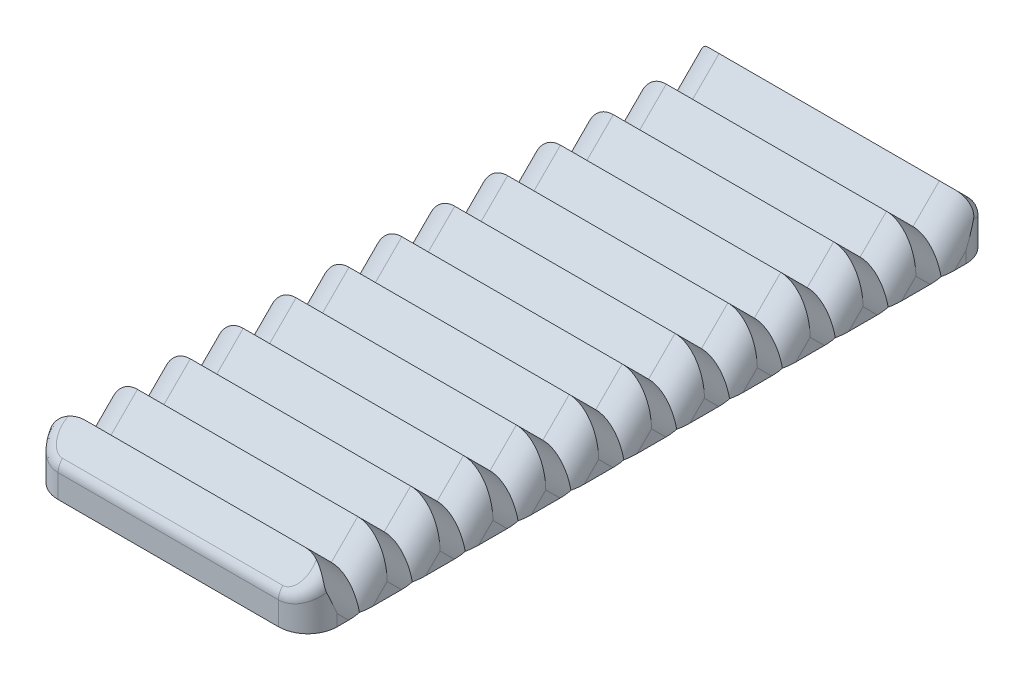
SolidWorks part; units mm, degrees
ref_plane "Front Plane" through (0, 0, 0) normal (0, 0, 1) x (1, 0, 0)
ref_plane "Top Plane" through (0, 0, 0) normal (0, 1, 0) x (1, 0, 0)
ref_plane "Right Plane" through (0, 0, 0) normal (1, 0, 0) x (0, 0, -1)
sketch "Sketch1" plane through (0, 0, 0) normal (1, 0, 0) x (0, 0, -1)
  line L0 (0, 0) -> (0.9, 0.9)
  line L1 (0.9, 0.9) -> (1.8, 0)
  line L2 (0, 0) -> (1.8, 0) construction
  line L3 (1.8, 0) -> (2.7, 0.9)
  line L4 (2.7, 0.9) -> (3.6, 0)
  line L5 (1.8, 0) -> (3.6, 0) construction
  line L6 (3.6, 0) -> (4.5, 0.9)
  line L7 (4.5, 0.9) -> (5.4, 0)
  line L8 (3.6, 0) -> (5.4, 0) construction
  line L9 (5.4, 0) -> (6.3, 0.9)
  line L10 (6.3, 0.9) -> (7.2, 0)
  line L11 (5.4, 0) -> (7.2, 0) construction
  line L12 (7.2, 0) -> (8.1, 0.9)
  line L13 (8.1, 0.9) -> (9, 0)
  line L14 (7.2, 0) -> (9, 0) construction
  line L15 (9, 0) -> (9.9, 0.9)
  line L16 (9.9, 0.9) -> (10.8, 0)
  line L17 (9, 0) -> (10.8, 0) construction
  line L18 (10.8, 0) -> (11.7, 0.9)
  line L19 (11.7, 0.9) -> (12.6, 0)
  line L20 (10.8, 0) -> (12.6, 0) construction
  line L21 (0, 0) -> (0, -1)
  line L22 (0, -1) -> (23.4, -1)
  line L23 (12.6, 0) -> (13.5, 0.9)
  line L24 (13.5, 0.9) -> (14.4, 0)
  line L25 (12.6, 0) -> (14.4, 0) construction
  line L26 (14.4, 0) -> (15.3, 0.9)
  line L27 (15.3, 0.9) -> (16.2, 0)
  line L28 (14.4, 0) -> (16.2, 0) construction
  line L29 (16.2, 0) -> (17.1, 0.9)
  line L30 (17.1, 0.9) -> (18, 0)
  line L31 (16.2, 0) -> (18, 0) construction
  line L32 (18, 0) -> (18.9, 0.9)
  line L33 (18.9, 0.9) -> (19.8, 0)
  line L34 (18, 0) -> (19.8, 0) construction
  line L35 (19.8, 0) -> (20.7, 0.9)
  line L36 (20.7, 0.9) -> (21.6, 0)
  line L37 (19.8, 0) -> (21.6, 0) construction
  line L38 (21.6, 0) -> (22.5, 0.9)
  line L39 (22.5, 0.9) -> (23.4, 0)
  line L40 (21.6, 0) -> (23.4, 0) construction
  line L41 (23.4, -1) -> (23.4, 0)
  dimension "D1" = 0.9
  dimension "D2" = 13
  dimension "D3" = 1
extrude "Boss-Extrude1" add sketch "Sketch1" along normal blind 9.5 contours L22 L41 L39 L38 L36 L35 L33 L32 L30 L29 L27 L26 L24 L23 L19 L18 L16 L15 L13 L12 L10 L9 L7 L6 L4 L3 L1 L0 L21 region at (0, -0.2517, -11.7)
fillet "Fillet1" radius 1 52 edges at (9.5, -0.5, -23.4) (9.5, -0.5, 0) (0, -0.5, 0) (0, -0.5, -23.4) (0, 0.45, -22.05) (0, 0.45, -21.15) (0, 0.45, -20.25) (0, 0.45, -19.35) (0, 0.45, -18.45) (0, 0.45, -17.55) (0, 0.45, -16.65) (0, 0.45, -15.75) (0, 0.45, -14.85) (0, 0.45, -13.95) (0, 0.45, -13.05) (0, 0.45, -12.15) (0, 0.45, -11.25) (0, 0.45, -10.35) (0, 0.45, -9.45) (0, 0.45, -8.55) (0, 0.45, -7.65) (0, 0.45, -6.75) (0, 0.45, -5.85) (0, 0.45, -4.95) (0, 0.45, -4.05) (0, 0.45, -3.15) (0, 0.45, -2.25) (0, 0.45, -1.35) (9.5, 0.45, -22.05) (9.5, 0.45, -21.15) (9.5, 0.45, -20.25) (9.5, 0.45, -19.35) (9.5, 0.45, -18.45) (9.5, 0.45, -17.55) (9.5, 0.45, -15.75) (9.5, 0.45, -16.65) (9.5, 0.45, -14.85) (9.5, 0.45, -13.95) (9.5, 0.45, -13.05) (9.5, 0.45, -12.15) (9.5, 0.45, -11.25) (9.5, 0.45, -10.35) (9.5, 0.45, -9.45) (9.5, 0.45, -8.55) (9.5, 0.45, -7.65) (9.5, 0.45, -6.75) (9.5, 0.45, -5.85) (9.5, 0.45, -4.95) (9.5, 0.45, -4.05) (9.5, 0.45, -3.15) (9.5, 0.45, -2.25) (9.5, 0.45, -1.35)
fillet "Fillet2" radius 0.5 6 edges at (9.0134, 0.1419, -0.1419) (0.4866, 0.1419, -0.1419) (9.0134, 0.1419, -23.2581) (0.4866, 0.1419, -23.2581) (4.75, 0, 0) (4.75, 0, -23.4)
